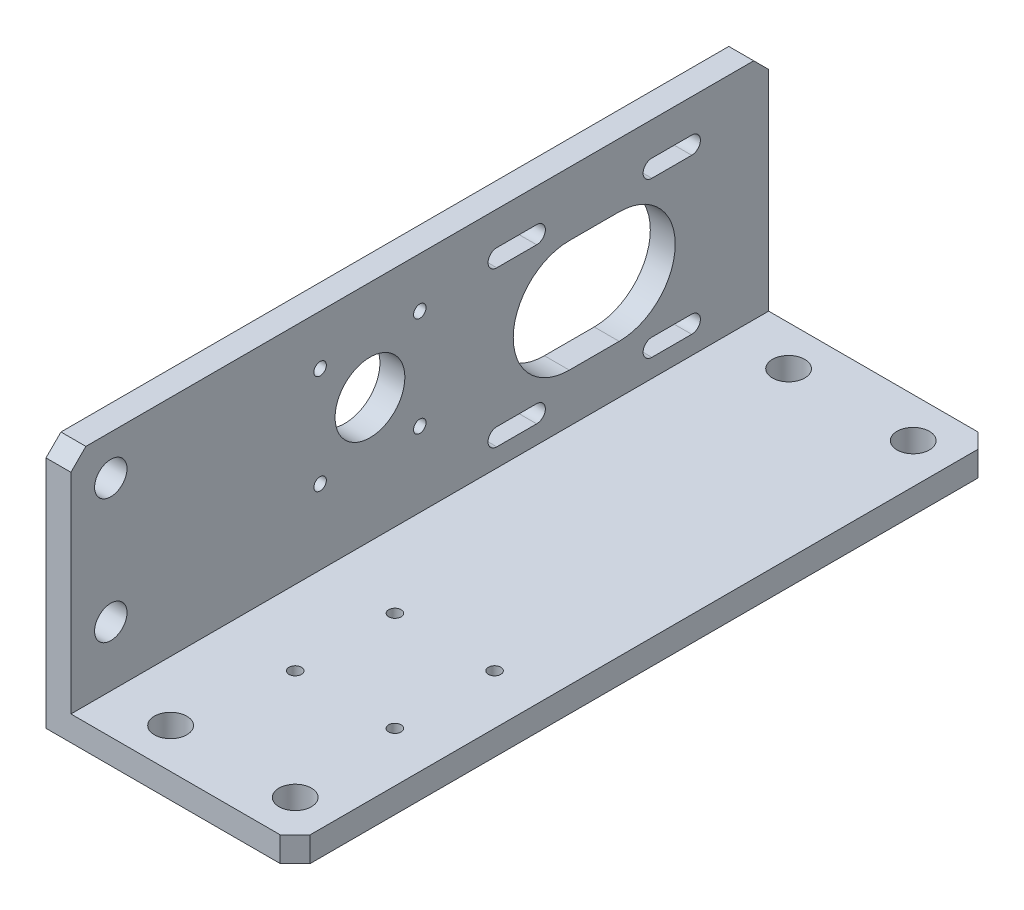
SolidWorks part; units mm, degrees
material "Lega 1060"
ref_plane "Piano frontale" through (0, 0, 0) normal (0, 0, 1) x (1, 0, 0)
ref_plane "Piano superiore" through (0, 0, 0) normal (0, 1, 0) x (1, 0, 0)
ref_plane "Piano destro" through (0, 0, 0) normal (1, 0, 0) x (0, 0, -1)
sketch "Schizzo1" plane through (0, 0, 0) normal (0, 0, 1) x (1, 0, 0)
  line L0 (0, 0) -> (0, 50)
  line L1 (0, 50) -> (5, 50)
  line L2 (5, 50) -> (5, 5)
  line L3 (5, 5) -> (50, 5)
  line L4 (50, 5) -> (50, 0)
  line L5 (50, 0) -> (0, 0)
  dimension "D1" = 5
  dimension "D2" = 5
  dimension "D3" = 50
  dimension "D4" = 50
extrude "Estrusione-Estrusione1" add sketch "Schizzo1" along normal blind 140
sketch "Schizzo2" plane through (0, 0, 0) normal (0, -1, 0) x (1, 0, 0)
  line L0 (5.4524, 132) -> (42.7933, 132) construction
  line L1 (0, 140) -> (50, 140) construction
  line L5 (50, 140) -> (50, 0) construction
  point P4 (17, 132)
  point P5 (42, 132)
  dimension "D1" = 8
  dimension "D2" = 25
  dimension "D3" = 8
sketch "Schizzo3" plane through (0, 0, 0) normal (-1, 0, 0) x (0, 0, 1)
  line L0 (132, 44.621) -> (132, 5.772) construction
  line L1 (140, 50) -> (140, 0) construction
  line L2 (140, 50) -> (0, 50) construction
  point P4 (132, 42)
  point P5 (132, 17)
  dimension "D1" = 8
  dimension "D2" = 8
  dimension "D3" = 25
hole_wizard "Foro Ø6.5 (6.5)-1" positions "Schizzo5" profile "Schizzo4" hole size "Ø6.5" standard "ISO" end condition through all
sketch "Schizzo5" plane through (0, 0, 0) normal (0, -1, 0) x (-1, 0, 0)
  point P0 (-17, -132)
  point P3 (-42, -132)
sketch "Schizzo4" plane through (17, 0, 132) normal (1, 0, 0) x (0, 0, -1)
  line L0 (0, 0) -> (0, 50)
  line L1 (0, 50) -> (3.25, 50)
  line L2 (3.25, 50) -> (3.25, 0)
  line L5 (3.25, 0) -> (0, 0)
  line L11 (0, -6.35) -> (0, 107.95) construction
  dimension "Thru Hole Dia." = 6.5
  dimension "Thru Hole Depth" = 50
hole_wizard "Foro Ø6.5 (6.5)-2" positions "Schizzo7" profile "Schizzo6" hole size "Ø6.5" standard "ISO"
sketch "Schizzo7" plane through (0, 0, 0) normal (-1, 0, 0) x (0, 0, 1)
  point P1 (132, 42)
  point P4 (132, 17)
sketch "Schizzo6" plane through (0, 42, 132) normal (0, 1, 0) x (0, 0, 1)
  line L0 (0, 0) -> (0, 6.9528)
  line L1 (0, 6.9528) -> (3.25, 5)
  line L2 (3.25, 5) -> (3.25, 0)
  line L5 (3.25, 0) -> (0, 0)
  line L10 (0, 6.9528) -> (-3.25, 5) construction
  line L11 (0, -6.35) -> (0, 107.95) construction
  dimension "Hole Dia." = 6.5
  dimension "Hole Depth" = 5
  dimension "Drill Angle" = 118
ref_plane "Piano1" through (0, 0, 70) normal (0, 0, 1) x (1, 0, 0)
mirror "Specchia1" about plane through (0, 0, 70) normal (0, 0, 1) of "Foro Ø6.5 (6.5)-1"
sketch "Schizzo10" plane through (0, 0, 0) normal (-1, 0, 0) x (0, 0, 1)
  line L3 (140, 50) -> (140, 0) construction
  line L5 (140, 50) -> (0, 50) construction
  circle A5 centre (80, 30) radius 7
  point P8 (80, 30)
  point P20 (80, 30)
  dimension "D7" = 14
  dimension "D5" = 60
  dimension "D6" = 20
extrude "Taglio-Estrusione3" cut sketch "Schizzo10" against normal up to next
sketch "Schizzo11" plane through (0, 0, 0) normal (0, -1, 0) x (1, 0, 0)
  line L0 (30, 100) -> (14.4837, 100) construction
  line L1 (30, 100) -> (4.5929, 74.5929) construction
  line L3 (50, 140) -> (50, 0) construction
  line L4 (0, 140) -> (50, 140) construction
  circle A0 centre (20, 90) radius 1.75
  circle A3 centre (20, 110) radius 1.75
  circle A4 centre (40, 110) radius 1.75
  circle A5 centre (40, 90) radius 1.75
  point P2 (30, 100)
  point P17 (30, 100)
  dimension "D2" = 3.5
  dimension "D1" = 20
  dimension "D3" = 45
  dimension "D5" = 20
  dimension "D6" = 40
  dimension "D4" = 4
sketch "Schizzo13" plane through (0, 0, 0) normal (-1, 0, 0) x (0, 0, 1)
  line L0 (60.9365, 26) -> (8.6526, 26) construction
  line L2 (140, 0) -> (0, 0) construction
  line L3 (15.4437, 41.5563) -> (23.4437, 41.5563) construction
  line L4 (15.4437, 43.3063) -> (23.4437, 43.3063)
  line L5 (15.4437, 39.8063) -> (23.4437, 39.8063)
  line L6 (15.4437, 10.4437) -> (23.4437, 10.4437) construction
  line L7 (15.4437, 8.6937) -> (23.4437, 8.6937)
  line L8 (15.4437, 12.1937) -> (23.4437, 12.1937)
  line L9 (35, 26) -> (35, 7.2619) construction
  line L10 (54.5563, 41.5563) -> (46.5563, 41.5563) construction
  line L11 (54.5563, 43.3063) -> (46.5563, 43.3063)
  line L12 (54.5563, 39.8063) -> (46.5563, 39.8063)
  line L13 (54.5563, 10.4437) -> (46.5563, 10.4437) construction
  line L14 (54.5563, 8.6937) -> (46.5563, 8.6937)
  line L15 (54.5563, 12.1937) -> (46.5563, 12.1937)
  line L16 (40, 26) -> (30, 26) construction
  line L17 (40, 14.75) -> (30, 14.75)
  line L18 (40, 37.25) -> (30, 37.25)
  arc A0 (54.5563, 43.3063) -> (54.5563, 39.8063) centre (54.5563, 41.5563) cw
  circle A1 centre (80, 30) radius 7 construction
  arc A2 (15.4437, 43.3063) -> (15.4437, 39.8063) centre (15.4437, 41.5563) ccw
  arc A3 (46.5563, 39.8063) -> (46.5563, 43.3063) centre (46.5563, 41.5563) cw
  arc A4 (15.4437, 8.6937) -> (15.4437, 12.1937) centre (15.4437, 10.4437) cw
  arc A5 (23.4437, 12.1937) -> (23.4437, 8.6937) centre (23.4437, 10.4437) cw
  arc A7 (23.4437, 39.8063) -> (23.4437, 43.3063) centre (23.4437, 41.5563) ccw
  arc A10 (54.5563, 8.6937) -> (54.5563, 12.1937) centre (54.5563, 10.4437) ccw
  arc A11 (46.5563, 12.1937) -> (46.5563, 8.6937) centre (46.5563, 10.4437) ccw
  arc A12 (40, 14.75) -> (40, 37.25) centre (40, 26) ccw
  arc A13 (30, 37.25) -> (30, 14.75) centre (30, 26) ccw
  point P8 (35, 26)
  point P13 (50.5563, 41.5563)
  point P17 (19.4437, 10.4437)
  point P19 (35, 26)
  point P22 (19.4437, 41.5563)
  point P40 (50.5563, 10.4437)
  point P47 (35, 26)
  dimension "D2" = 22.5
  dimension "D3" = 10
  dimension "D5" = 26
  dimension "D6" = 45
  dimension "D8" = 3.5
  dimension "D9" = 8
extrude "Taglio-Estrusione6" cut sketch "Schizzo13" against normal up to next
chamfer "Smusso1" distance 3 angle 45 4 edges at (50, 2.5, 0) (2.5, 50, 0) (50, 2.5, 140) (2.5, 50, 140)
sketch "Sketch1" plane through (0, 0, 0) normal (-1, 0, 0) x (0, 0, 1)
  line L0 (80, 30) -> (80, 46.7736) construction
  line L1 (80, 46.7736) -> (80, 30) construction
  line L2 (80, 30) -> (63.2264, 46.7736) construction
  line L3 (63.2264, 46.7736) -> (80, 30) construction
  line L4 (80, 30) -> (62.4784, 30) construction
  point P3 (70, 40)
  point P6 (90, 40)
  point P7 (70, 20)
  point P8 (90, 20)
  dimension "D1" = 45
  dimension "D2" = 10
hole_wizard "M3 Tapped Hole1" positions "3DSketch1" profile "Sketch2" tap size "M3" standard "ISO" end condition through all
sketch3d "3DSketch1"
  point P0 (0, 40, 70)
  point P3 (0, 40, 90)
  point P6 (0, 20, 90)
  point P9 (0, 20, 70)
sketch "Sketch2" plane through (0, 40, 70) normal (0, 1, 0) x (0, 0, 1)
  line L0 (0, 0) -> (0, 50)
  line L1 (0, 50) -> (1.25, 50)
  line L2 (1.25, 50) -> (1.25, 0)
  line L5 (1.25, 0) -> (0, 0)
  line L11 (0, -6.35) -> (0, 107.95) construction
  dimension "Thru Tap Drill Dia." = 2.5
  dimension "Thru Tap Drill Depth" = 50
cosmetic thread "Cosmetic Thread1" parameters "D2"=3
cosmetic thread "Cosmetic Thread2" parameters "D2"=3
cosmetic thread "Cosmetic Thread3" parameters "D2"=3
cosmetic thread "Cosmetic Thread4" parameters "D2"=3
hole_wizard "M3 Tapped Hole2" positions "3DSketch2" profile "Sketch3" tap size "M3" standard "ISO" end condition through all
sketch3d "3DSketch2"
  point P0 (20, 0, 110)
  point P3 (40, 0, 110)
  point P6 (40, 0, 90)
  point P9 (20, 0, 90)
sketch "Sketch3" plane through (20, 0, 110) normal (1, 0, 0) x (0, 0, -1)
  line L0 (0, 0) -> (0, 50)
  line L1 (0, 50) -> (1.25, 50)
  line L2 (1.25, 50) -> (1.25, 0)
  line L5 (1.25, 0) -> (0, 0)
  line L11 (0, -6.35) -> (0, 107.95) construction
  dimension "Thru Tap Drill Dia." = 2.5
  dimension "Thru Tap Drill Depth" = 50
cosmetic thread "Cosmetic Thread5" parameters "D2"=3
cosmetic thread "Cosmetic Thread6" parameters "D2"=3
cosmetic thread "Cosmetic Thread7" parameters "D2"=3
cosmetic thread "Cosmetic Thread8" parameters "D2"=3
